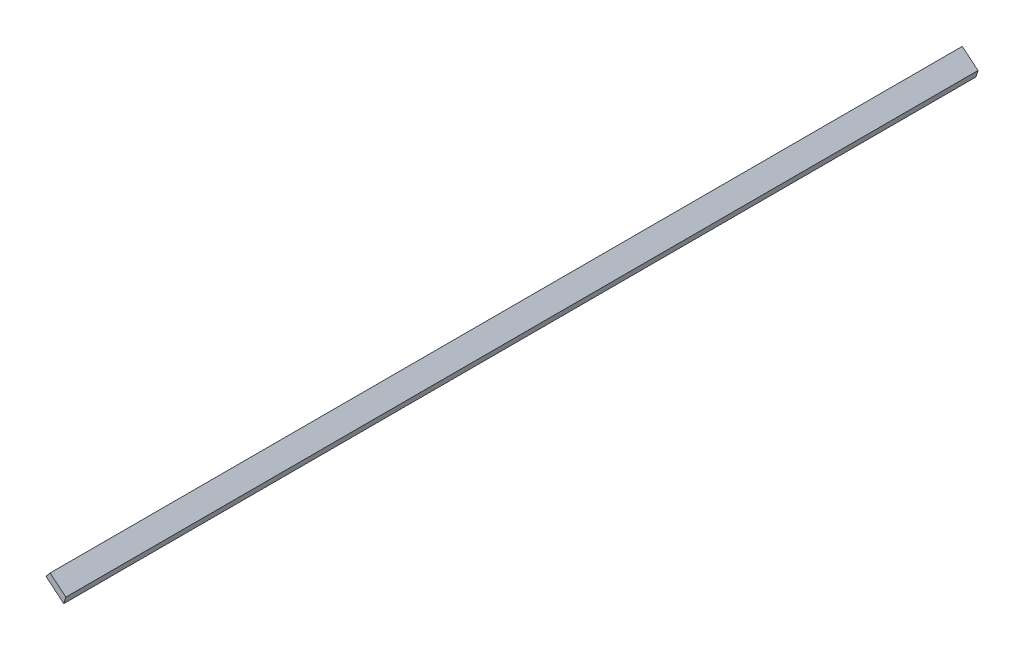
SolidWorks part; units mm, degrees
ref_plane "Front Plane" through (0, 0, 0) normal (0, 0, 1) x (1, 0, 0)
ref_plane "Top Plane" through (0, 0, 0) normal (0, 1, 0) x (1, 0, 0)
ref_plane "Right Plane" through (0, 0, 0) normal (1, 0, 0) x (0, 0, -1)
sketch "Sketch1" plane through (0, 0, 0) normal (0, 0, 1) x (1, 0, 0)
  line L0 (0, 0) -> (2.0444, 6.5621)
  line L1 (2.0444, 6.5621) -> (-13.3712, 19.4076)
  line L2 (-13.3712, 19.4076) -> (-17.4362, 14.5293)
  line L3 (-17.4362, 14.5293) -> (0, 0)
  dimension "D1" = 6.35
  dimension "D2" = 90
  dimension "D3" = 67.5
  dimension "D4" = 20.066
extrude "Boss-Extrude1" add sketch "Sketch1" along normal blind 895.35
